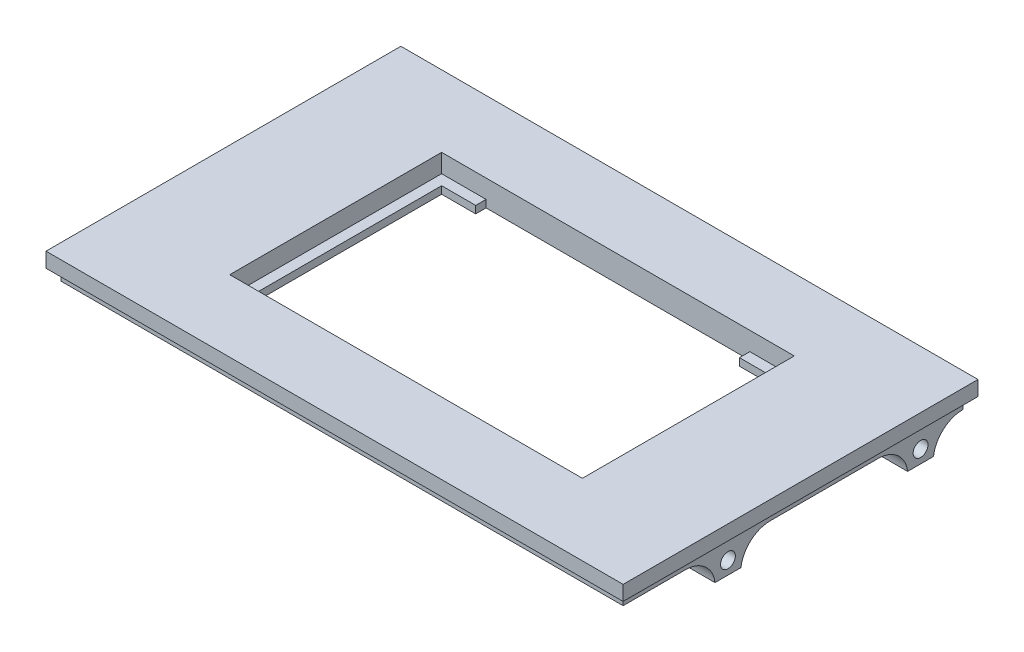
SolidWorks part; units mm, degrees
ref_plane "前视基准面" through (0, 0, 0) normal (0, 0, 1) x (1, 0, 0)
ref_plane "上视基准面" through (0, 0, 0) normal (0, 1, 0) x (1, 0, 0)
ref_plane "右视基准面" through (0, 0, 0) normal (1, 0, 0) x (0, 0, -1)
other "Configuration Table"
sketch "草图1" plane through (0, 0, 0) normal (0, 1, 0) x (1, 0, 0)
  line L1 (0, 0) -> (77.9, 0)
  line L2 (0, 0) -> (0, 47.9)
  line L3 (0, 47.9) -> (77.9, 47.9)
  line L4 (77.9, 0) -> (77.9, 47.9)
  dimension "D1" = 47.9
  dimension "D2" = 77.9
extrude "凸台-拉伸1" add sketch "草图1" along normal blind 2
sketch "草图2" plane through (0, 2, 0) normal (0, 1, 0) x (1, 0, 0)
  line L0 (0, 23.95) -> (77.9, 23.95) construction
  line L1 (0, 47.9) -> (0, 0) construction
  line L2 (77.9, 0) -> (77.9, 47.9) construction
  line L4 (15.15, 9.65) -> (62.75, 9.65)
  line L5 (15.15, 9.65) -> (15.15, 38.25)
  line L6 (15.15, 38.25) -> (62.75, 38.25)
  line L7 (62.75, 9.65) -> (62.75, 38.25)
  line L8 (15.15, 9.65) -> (62.75, 38.25) construction
  line L9 (15.15, 38.25) -> (62.75, 9.65) construction
  point P6 (38.95, 23.95)
  dimension "D1" = 28.6
  dimension "D2" = 47.6
extrude "切除-拉伸1" cut sketch "草图2" against normal blind 27
sketch "草图4" plane through (0, 0, 0) normal (0, -1, 0) x (1, 0, 0)
  line L12 (15.15, -38.25) -> (62.75, -38.25) construction
  line L13 (62.75, -9.65) -> (15.15, -9.65) construction
  line L14 (15.15, -9.65) -> (15.15, -38.25) construction
  line L15 (62.75, -38.25) -> (62.75, -9.65) construction
  line L16 (15.15, -38.25) -> (62.75, -38.25)
  line L17 (62.75, -9.65) -> (15.15, -9.65)
  line L18 (15.15, -9.65) -> (15.15, -38.25)
  line L19 (62.75, -38.25) -> (62.75, -9.65)
  line L20 (0, -23.95) -> (77.9, -23.95) construction
  line L21 (0, -47.9) -> (0, 0) construction
  line L22 (77.9, 0) -> (77.9, -47.9) construction
  line L24 (76.9, -46.9) -> (1, -46.9)
  line L25 (76.9, -46.9) -> (76.9, -1)
  line L26 (76.9, -1) -> (1, -1)
  line L27 (1, -46.9) -> (1, -1)
  line L28 (76.9, -46.9) -> (1, -1) construction
  line L29 (76.9, -1) -> (1, -46.9) construction
  point P10 (38.95, -23.95)
  dimension "D1" = 45.9
  dimension "D2" = 75.9
extrude "凸台-拉伸3" add sketch "草图4" along normal blind 0.5
sketch "草图5" plane through (0, -0.5, 0) normal (0, -1, 0) x (1, 0, 0)
  line L8 (61.35, -36.85) -> (61.35, -11.05)
  line L9 (61.35, -11.05) -> (56.75, -11.05)
  line L10 (16.55, -11.05) -> (16.55, -36.85)
  line L11 (16.55, -36.85) -> (21.15, -36.85)
  line L12 (21.15, -9.65) -> (21.15, -11.05)
  line L13 (62.75, -9.65) -> (15.15, -9.65) construction
  line L14 (15.15, -38.25) -> (62.75, -38.25) construction
  line L15 (56.75, -9.65) -> (56.75, -11.05)
  line L16 (1, -1) -> (1, -46.9)
  line L17 (1, -46.9) -> (76.9, -46.9)
  line L18 (76.9, -46.9) -> (76.9, -1)
  line L19 (76.9, -1) -> (1, -1)
  line L20 (1, -1) -> (1, -46.9)
  line L21 (1, -46.9) -> (76.9, -46.9)
  line L22 (76.9, -46.9) -> (76.9, -1)
  line L23 (76.9, -1) -> (1, -1)
  line L24 (15.15, -9.65) -> (15.15, -38.25) construction
  line L25 (62.75, -38.25) -> (62.75, -9.65) construction
  line L26 (21.15, -36.85) -> (21.15, -38.25)
  line L27 (21.15, -11.05) -> (16.55, -11.05)
  line L28 (56.75, -36.85) -> (61.35, -36.85)
  line L29 (56.75, -36.85) -> (56.75, -38.25)
  line L30 (21.6401, -9.65) -> (56.75, -9.65)
  line L31 (56.75, -38.25) -> (21.15, -38.25)
  line M15 (1, -1) -> (1, -46.9)
  line M16 (1, -46.9) -> (76.9, -46.9)
  line M17 (76.9, -46.9) -> (76.9, -1)
  line M18 (76.9, -1) -> (1, -1)
  line M19 (62.75, -38.25) -> (15.15, -38.25)
  line M20 (15.15, -38.25) -> (15.15, -9.65)
  line M21 (15.15, -9.65) -> (62.75, -9.65)
  line M22 (62.75, -9.65) -> (62.75, -38.25)
  dimension "D2" = 6
  dimension "D3" = 6
  dimension "D1" = 0
extrude "凸台-拉伸4" add sketch "草图5" along normal blind 1 contours M18 M15 M16 M17 M22 M19 M20 M21 | L27 L12 L26 L11 L10 M21 M20 M19 | L28 L29 L15 L9 L8 M19 M22 M21 region at (61.6422, -0.5, -23.95) region at (18.15, -0.5, -37.9578) region at (38.95, -0.5, -1.887)
sketch "草图8" plane through (76.9, 0, 0) normal (1, 0, 0) x (0, 0, -1)
  line L0 (46.9, -1.5) -> (1, -1.5) construction
  line L1 (42.9, -1.5) -> (39.4, -1.5)
  line L2 (42.9, -1.5) -> (42.9, -5)
  line L3 (42.9, -5) -> (39.4, -5)
  line L4 (39.4, -1.5) -> (39.4, -5)
  line L5 (46.9, -1.5) -> (46.9, 0) construction
  line L6 (16.9, -1.5) -> (13.4, -1.5)
  line L7 (16.9, -1.5) -> (16.9, -5)
  line L8 (16.9, -5) -> (13.4, -5)
  line L9 (13.4, -1.5) -> (13.4, -5)
  line L10 (39.4, -3.25) -> (42.9, -3.25) construction
  line L11 (13.4, -3.25) -> (16.9, -3.25) construction
  line L12 (0, 2) -> (47.9, 2) construction
  line L13 (47.9, 2) -> (47.9, 0) construction
  circle A0 centre (41.15, -3.25) radius 1
  circle A1 centre (15.15, -3.25) radius 1
  point P12 (46.9, -0.75)
  dimension "D4" = 2
  dimension "D8" = 2
  dimension "D1" = 4
  dimension "D2" = 3.5
  dimension "D3" = 3.5
  dimension "D5" = 3.5
  dimension "D6" = 3.5
  dimension "D7" = 30
extrude "凸台-拉伸5" add sketch "草图8" against normal blind 4
fillet "圆角1" radius 4 4 edges at (74.9, -1.5, -42.9) (74.9, -1.5, -16.9) (74.9, -1.5, -13.4) (74.9, -1.5, -39.4)
ref_plane "基准面1" through (38.95, 0, 0) normal (1, 0, 0) x (0, 0, -1)
mirror "镜向1" about plane through (38.95, 0, 0) normal (1, 0, 0) of "圆角1", "凸台-拉伸5"
